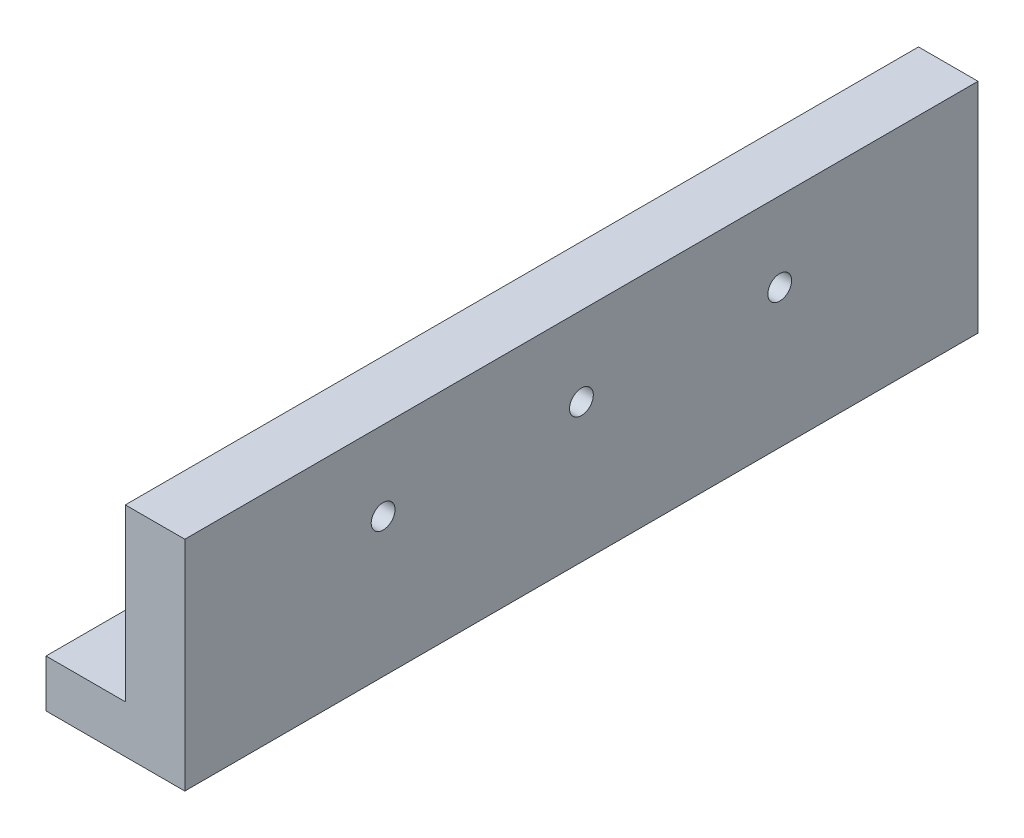
SolidWorks part; units mm, degrees
ref_plane "前基準面" through (0, 0, 0) normal (0, 0, 1) x (1, 0, 0)
ref_plane "上基準面" through (0, 0, 0) normal (0, 1, 0) x (1, 0, 0)
ref_plane "右基準面" through (0, 0, 0) normal (1, 0, 0) x (0, 0, -1)
sketch "草圖1" plane through (0, 0, 0) normal (0, 0, 1) x (1, 0, 0)
  line L0 (-5.0196, 208.8052) -> (-5.0196, 165.8052)
  line L2 (-5.0196, 165.8052) -> (-25.0196, 165.8052)
  line L3 (-25.0196, 165.8052) -> (-25.0196, 153.8052)
  line L4 (-25.0196, 153.8052) -> (9.9804, 153.8052)
  line L5 (9.9804, 153.8052) -> (9.9804, 208.8052)
  line L6 (9.9804, 208.8052) -> (-5.0196, 208.8052)
  dimension "D1" = 35
  dimension "D2" = 12
  dimension "D3" = 55
  dimension "D4" = 15
extrude "填料-伸長1" add sketch "草圖1" against normal blind 200
sketch "草圖2" plane through (9.9804, 0, 0) normal (1, 0, 0) x (0, 0, -1)
  line L0 (200, 208.8052) -> (0, 208.8052) construction
  line L3 (200, 153.8052) -> (200, 208.8052) construction
  circle A2 centre (150, 188.8052) radius 3
  dimension "D1" = 20
  dimension "D3" = 6
  dimension "D7" = 50
extrude "除料-伸長1" cut sketch "草圖2" against normal up to surface (15 mm away) and the other way through all up to face at (-5.0196, 187.3052, -100)
pattern_linear "LPattern1" count 3 spacing 50 along (0, 0, 1) of "除料-伸長1"
